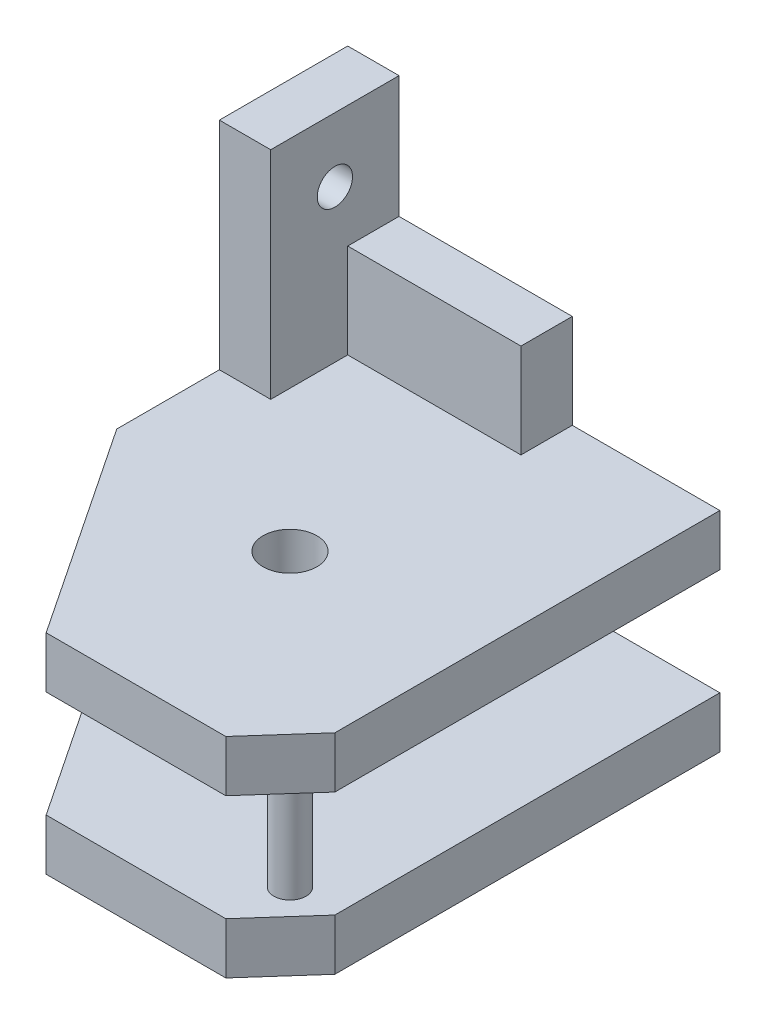
SolidWorks part; units mm, degrees
ref_plane "前视基准面" through (0, 0, 0) normal (0, 0, 1) x (1, 0, 0)
ref_plane "上视基准面" through (0, 0, 0) normal (0, 1, 0) x (1, 0, 0)
ref_plane "右视基准面" through (0, 0, 0) normal (1, 0, 0) x (0, 0, -1)
other "Configuration Table"
sketch "草图1" plane through (0, 0, 0) normal (0, 0, 1) x (1, 0, 0)
  line L1 (0, -50) -> (8, -50)
  line L2 (0, -50) -> (0, 50)
  line L3 (0, 50) -> (8, 50)
  line L4 (8, -50) -> (8, 50)
extrude "凸台-拉伸2" add sketch "草图1" along normal blind 20
sketch "草图2" plane through (0, 0, 0) normal (0, 0, 1) x (1, 0, 0)
  line L0 (8, -50) -> (8, 50) construction
  line L1 (8, -16.3) -> (35, -16.3)
  line L2 (8, -16.3) -> (8, -31)
  line L3 (8, -31) -> (35, -31)
  line L4 (35, -16.3) -> (35, -31)
  line L6 (8, 16.3) -> (35, 16.3)
  line L7 (8, 16.3) -> (8, 31)
  line L8 (8, 31) -> (35, 31)
  line L9 (35, 16.3) -> (35, 31)
extrude "凸台-拉伸4" add sketch "草图2" along normal blind 8
sketch "草图4" plane through (0, 0, 0) normal (0, 1, 0) x (1, 0, 0)
  line L0 (0, 0) -> (58, 0)
  line L1 (58, 0) -> (58, -60)
  line L2 (58, -60) -> (50, -69)
  line L3 (50, -69) -> (22, -69)
  line L4 (22, -69) -> (0, -36)
  line L5 (0, -36) -> (0, 0)
extrude "凸台-拉伸6" add sketch "草图4" against normal mid plane 32.6
sketch "草图5" plane through (0, 0, 0) normal (0, 1, 0) x (1, 0, 0)
  line L0 (8, 0) -> (58, 0)
  line L1 (58, 0) -> (58, -60)
  line L2 (58, -60) -> (50, -69)
  line L3 (50, -69) -> (22, -69)
  line L4 (22, -69) -> (0, -36)
  line L5 (0, -36) -> (0, -20)
  line L6 (0, -20) -> (8, -20)
  line L7 (8, -20) -> (8, 0)
extrude "切除-拉伸1" cut sketch "草图5" against normal mid plane 16.6
sketch "草图6" plane through (0, 0, 0) normal (0, 1, 0) x (1, 0, 0)
  circle A0 centre (30, -39) radius 5.5
extrude "凸台-拉伸7" add sketch "草图6" against normal mid plane 16.6
sketch "草图7" plane through (0, 0, 0) normal (0, 1, 0) x (1, 0, 0)
  circle A0 centre (30, -39) radius 5.5
extrude "切除-拉伸2" cut sketch "草图7" against normal mid plane 15
sketch "草图8" plane through (0, 0, 0) normal (0, 1, 0) x (1, 0, 0)
  circle A0 centre (50.7182, -59.7182) radius 2.5
extrude "凸台-拉伸8" add sketch "草图8" against normal mid plane 16.6
sketch "草图9" plane through (0, 0, 0) normal (0, 1, 0) x (1, 0, 0)
  circle A0 centre (30, -39) radius 4.2
extrude "切除-拉伸3" cut sketch "草图9" against normal mid plane 42.6
sketch "草图11" plane through (0, 0, 0) normal (1, 0, 0) x (0, 0, -1)
  circle A0 centre (-10, -40) radius 2.75
  circle A1 centre (-10, 40) radius 2.75
extrude "切除-拉伸5" cut sketch "草图11" against normal mid plane 26
